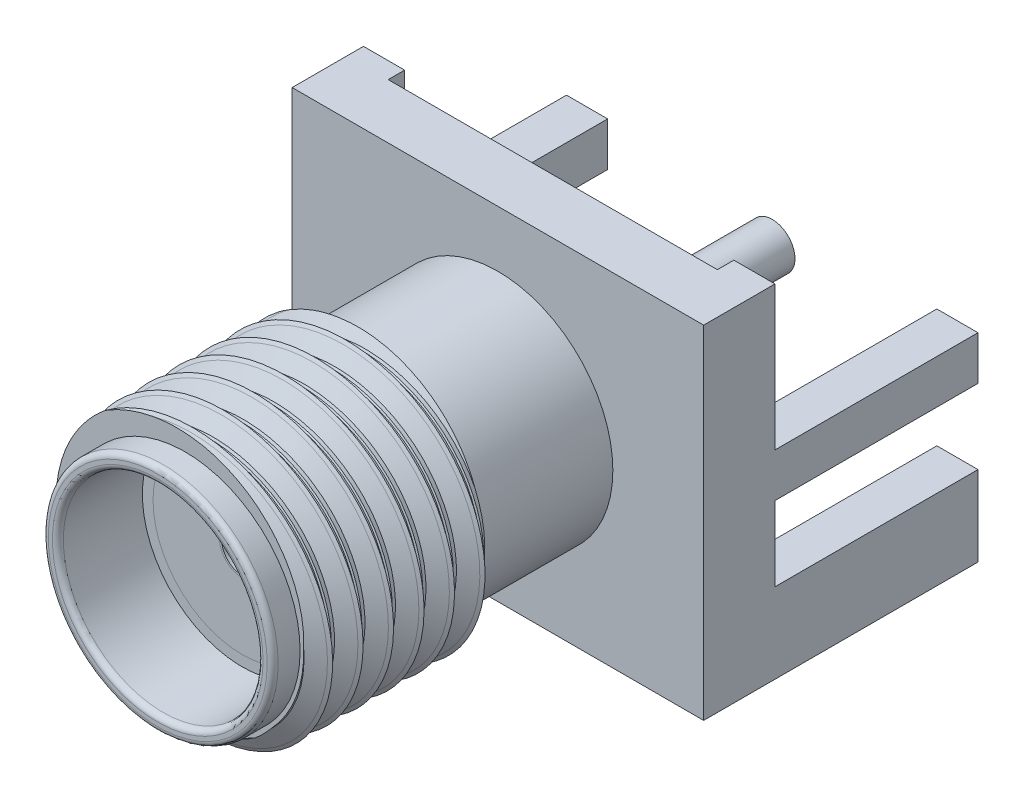
SolidWorks part; units mm, degrees
material "Brass"
ref_plane "Front Plane" through (0, 0, 0) normal (0, 0, 1) x (1, 0, 0)
ref_plane "Top Plane" through (0, 0, 0) normal (0, 1, 0) x (1, 0, 0)
ref_plane "Right Plane" through (0, 0, 0) normal (1, 0, 0) x (0, 0, -1)
sketch "Sketch1" plane through (0, 0, 0) normal (0, 0, 1) x (1, 0, 0)
  circle A0 centre (0, 0) radius 2.6607
  dimension "D1" = 5.3213
extrude "Boss-Extrude1" add sketch "Sketch1" along normal blind 7.874
sketch "Sketch2" plane through (0, 0, 7.874) normal (0, 0, 1) x (1, 0, 0)
  circle A0 centre (0, 0) radius 2.3114
  dimension "D1" = 4.6228
extrude "Cut-Extrude1" cut sketch "Sketch2" against normal blind 1.9558
sketch "Sketch5" plane through (0, 0, 0) normal (0, 0, -1) x (-1, 0, 0)
  line L0 (0, 2.6607) -> (0, 3.9624) construction
  line L1 (-4.7625, 3.9624) -> (4.7625, 3.9624)
  line L2 (-4.7625, 3.9624) -> (-4.7625, -3.9624)
  line L3 (-4.7625, -3.9624) -> (4.7625, -3.9624)
  line L4 (4.7625, 3.9624) -> (4.7625, -3.9624)
  line L5 (2.6607, 0) -> (4.7625, 0) construction
  circle A0 centre (0, 0) radius 2.6607 construction
  circle A1 centre (0, 0) radius 2.6607 construction
  circle A2 centre (0, 0) radius 2.032
  dimension "D3" = 4.064
  dimension "D1" = 9.525
  dimension "D2" = 7.9248
extrude "Boss-Extrude2" add sketch "Sketch5" along normal blind 1.651 separate body
sketch "Sketch6" plane through (0, 3.9624, 0) normal (0, 1, 0) x (1, 0, 0)
  line L0 (-4.7625, 1.651) -> (4.7625, 1.651) construction
  line L1 (-3.81, 1.651) -> (3.81, 1.651)
  line L2 (-3.81, 1.651) -> (-3.81, 1.27)
  line L3 (-3.81, 1.27) -> (3.81, 1.27)
  line L4 (3.81, 1.651) -> (3.81, 1.27)
  line L5 (-4.7625, 0) -> (4.7625, 0) construction
  line L6 (0, 1.27) -> (0, 0) construction
  dimension "D1" = 1.27
  dimension "D2" = 7.62
extrude "Cut-Extrude2" cut sketch "Sketch6" against normal through all
sketch "Sketch7" plane through (0, 0, 5.9182) normal (0, 0, 1) x (1, 0, 0)
  circle A0 centre (0, 0) radius 0.4763
  dimension "D1" = 0.9525
extrude "Cut-Extrude3" cut sketch "Sketch7" against normal through all
sketch "Sketch8" plane through (0, 0, 5.9182) normal (0, 0, 1) x (1, 0, 0)
  circle A0 centre (0, 0) radius 2.0638
  circle A4 centre (0, 0) radius 0.5259
  circle A5 centre (0, 0) radius 0.5259
  dimension "D1" = 4.1275
  dimension "D2" = 0.0496
split line "Split Line1"
sketch "Sketch9" plane through (0, 0, 0) normal (0, 0, 1) x (1, 0, 0)
  circle A0 centre (0, 0) radius 0.5259 construction
  circle A1 centre (0, 0) radius 0.5259
extrude "Boss-Extrude4" add sketch "Sketch9" against normal offset from surface (6.35 mm away) 5.08 separate body up to face at (2.032, 0, -1.27) offset beyond the face yes
sketch "Sketch10" plane through (0, 0, -1.651) normal (0, 0, -1) x (-1, 0, 0)
  line L0 (3.81, -3.9624) -> (3.81, 3.9624) construction
  line L1 (3.81, 0.635) -> (4.7625, 0.635)
  line L2 (3.81, 0.635) -> (3.81, -0.381)
  line L3 (3.81, -0.381) -> (4.7625, -0.381)
  line L4 (4.7625, 0.635) -> (4.7625, -0.381)
  line L5 (4.7625, -3.9624) -> (4.7625, 3.9624) construction
  line L7 (3.81, -2.1082) -> (4.7625, -2.1082)
  line L8 (3.81, -2.1082) -> (3.81, -3.9624)
  line L9 (3.81, -3.9624) -> (4.7625, -3.9624)
  line L10 (4.7625, -2.1082) -> (4.7625, -3.9624)
  line L11 (3.81, -3.9624) -> (4.7625, -3.9624) construction
  line L12 (0, -1000) -> (0, 49000) construction
  line L13 (-4.7625, -2.1082) -> (-4.7625, -3.9624)
  line L14 (-3.81, -3.9624) -> (-4.7625, -3.9624)
  line L15 (-3.81, -2.1082) -> (-3.81, -3.9624)
  line L16 (-3.81, -2.1082) -> (-4.7625, -2.1082)
  line L17 (-4.7625, 0.635) -> (-4.7625, -0.381)
  line L18 (-3.81, -0.381) -> (-4.7625, -0.381)
  line L19 (-3.81, 0.635) -> (-3.81, -0.381)
  line L20 (-3.81, 0.635) -> (-4.7625, 0.635)
  dimension "D1" = 1.016
  dimension "D2" = 1.7272
  dimension "D3" = 1.8542
extrude "Boss-Extrude5" add sketch "Sketch10" along normal up to surface (4.699 mm away) up to face at (0.5259, 0, -6.35)
sketch "Sketch12" plane through (0, 0, 7.874) normal (0, 0, 1) x (1, 0, 0)
  circle A1 centre (0, 0) radius 3.1636
  dimension "MajorDiameter" = 6.3271
sketch "Sketch13" plane through (0, 0, 7.874) normal (0, 0, 1) x (1, 0, 0)
  circle A0 centre (0, 0) radius 3.1636
  circle A1 centre (0, 0) radius 2.6607
  circle A2 centre (0, 0) radius 2.6607 construction
  dimension "MajorDiameter" = 6.3271
extrude "Boss-Extrude6" add sketch "Sketch13" against normal blind 4.191 from offset 0.635 offset against normal yes
curve "Helix/Spiral1" pitch 0.7056 height 7.0556 radius 3.1636 centre (0, 0, 7.874) axis (0, 0, -1) start towards (0, 1, 0) parameters "Pitch"=0.7056
sketch "Sketch15" plane through (0, 0, 0) normal (1, 0, 0) x (0, 0, -1)
  line L0 (-7.874, 3.1636) -> (-7.874, -3.1636) construction
  line L1 (-6.4629, 3.1636) -> (-7.1684, 3.1636) construction
  line L2 (-7.1684, 3.1636) -> (-7.874, 3.1636) construction
  line L3 (-10.4133, 2.7445) -> (0, 2.7445) construction
  line L4 (-10.4133, 2.7445) -> (-10.4133, -2.7445) construction
  line L5 (-7.874, 0) -> (-10.4133, 0) construction
  line L6 (0, 3.9624) -> (0, -3.9624) construction
  line L7 (-6.4629, 3.1636) -> (-5.7573, 3.1636) construction
  line L8 (-8.4915, 3.0883) -> (-8.4033, 3.0883) construction
  line L9 (-8.4033, 3.0883) -> (-8.2048, 2.7445)
  line L10 (-8.2048, 2.7445) -> (-8.1166, 2.7445)
  line L11 (-7.874, 2.6607) -> (-7.874, -2.6607) construction
  line L12 (-3.048, 3.1636) -> (-7.239, 3.1636) construction
  line L13 (-8.1166, 2.7445) -> (-7.9181, 3.0883)
  line L14 (-7.9181, 3.0883) -> (-7.8299, 3.0883) construction
  line L15 (-7.8299, 3.0883) -> (-7.6314, 2.7445)
  line L16 (-7.6314, 2.7445) -> (-7.5432, 2.7445)
  line L17 (-7.5432, 2.7445) -> (-7.3447, 3.0883)
  line L18 (-7.3447, 3.0883) -> (-7.2565, 3.0883) construction
  line L19 (-8.1607, 2.7445) -> (-8.1607, 3.9348) construction
  line L20 (-7.9181, 3.0883) -> (-8.4033, 3.0883) construction
  line L21 (-7.5873, 2.7445) -> (-7.5873, 3.9348) construction
  line L22 (-7.3447, 3.0883) -> (-7.8299, 3.0883) construction
  line L23 (-7.874, 3.1636) -> (-7.874, 3.9348) construction
  line L24 (-7.9181, 3.0883) -> (-7.874, 3.1636)
  line L25 (-7.874, 3.1636) -> (-7.8299, 3.0883)
  line L26 (-7.3447, 3.0883) -> (-7.3447, 4.147)
  line L27 (-7.3447, 4.147) -> (-8.4033, 4.147)
  line L28 (-8.4033, 4.147) -> (-8.4033, 3.0883)
  spline S0 degree 3 poles (30.3197, -1996.2874) (-9.6986, -238.0579) (-8.6725, 16.4609) (-7.7858, 2.2952) (-7.7417, 1.2422) (-7.6976, 0) (-7.6535, -1.2422) (-7.6094, -2.2952) (-7.5653, -2.9988) (-7.5212, -3.2459) (-7.4771, -2.9988) (-7.433, -2.2952) (-7.3889, -1.2422) (-7.3448, 0) (-7.3007, 1.2422) (-7.2566, 2.2952) (-7.2125, 2.9988) (-7.1684, 3.2459) (-7.1243, 2.9988) (-7.0803, 2.2952) (-7.0362, 1.2422) (-6.9921, 0) (-6.948, -1.2422) (-6.9039, -2.2952) (-6.8598, -2.9988) (-6.8157, -3.2459) (-6.7716, -2.9988) (-6.7275, -2.2952) (-6.6834, -1.2422) (-6.6393, 0) (-6.5952, 1.2422) (-6.5511, 2.2952) (-6.507, 2.9988) (-6.4629, 3.2459) (-6.4188, 2.9988) (-6.3747, 2.2952) (-6.3306, 1.2422) (-6.2865, 0) (-6.2424, -1.2422) (-6.1983, -2.2952) (-6.1542, -2.9988) (-6.1101, -3.2459) (-6.066, -2.9988) (-6.0219, -2.2952) (-5.9778, -1.2422) (-5.9337, 0) (-5.8896, 1.2422) (-5.8455, 2.2952) (-5.8014, 2.9988) (-5.7573, 3.2459) (-5.7132, 2.9988) (-5.6691, 2.2952) (-5.625, 1.2422) (-5.5809, 0) (-5.5368, -1.2422) (-5.4927, -2.2952) (-5.4487, -2.9988) (-5.4046, -3.2459) (-5.3605, -2.9988) (-5.3164, -2.2952) (-5.2723, -1.2422) (-5.2282, 0) (-5.1841, 1.2422) (-5.14, 2.2952) (-5.0959, 2.9988) (-5.0518, 3.2459) (-5.0077, 2.9988) (-4.9636, 2.2952) (-4.9195, 1.2422) (-4.8754, 0) (-4.8313, -1.2422) (-4.7872, -2.2952) (-4.7431, -2.9988) (-4.699, -3.2459) (-4.6549, -2.9988) (-4.6108, -2.2952) (-4.5667, -1.2422) (-4.5226, 0) (-4.4785, 1.2422) (-4.4344, 2.2952) (-4.3903, 2.9988) (-4.3462, 3.2459) (-4.3021, 2.9988) (-4.258, 2.2952) (-4.2139, 1.2422) (-4.1698, 0) (-4.1257, -1.2422) (-4.0816, -2.2952) (-4.0375, -2.9988) (-3.9934, -3.2459) (-3.9493, -2.9988) (-3.9052, -2.2952) (-3.8612, -1.2422) (-3.8171, 0) (-3.773, 1.2422) (-3.7289, 2.2952) (-3.6848, 2.9988) (-3.6407, 3.2459) (-3.5966, 2.9988) (-3.5525, 2.2952) (-3.5084, 1.2422) (-3.4643, 0) (-3.4202, -1.2422) (-3.3761, -2.2952) (-3.332, -2.9988) (-3.2879, -3.2459) (-3.2438, -2.9988) (-3.1997, -2.2952) (-3.1556, -1.2422) (-3.1115, 0) (-3.0674, 1.2422) (-3.0233, 2.2952) (-2.9792, 2.9988) (-2.9351, 3.2459) (-2.891, 2.9988) (-2.8469, 2.2952) (-2.8028, 1.2422) (-2.7587, 0) (-2.7146, -1.2422) (-2.6705, -2.2952) (-2.6264, -2.9988) (-2.5823, -3.2459) (-2.5382, -2.9988) (-2.4941, -2.2952) (-2.45, -1.2422) (-2.4059, 0) (-2.3618, 1.2422) (-2.3177, 2.2952) (-2.2737, 2.9988) (-2.2296, 3.2459) (-2.1855, 2.9988) (-2.1414, 2.2952) (-2.0973, 1.2422) (-2.0532, 0) (-2.0091, -1.2422) (-1.965, -2.2952) (-1.9209, -2.9988) (-1.8768, -3.2459) (-1.8327, -2.9988) (-1.7886, -2.2952) (-1.7445, -1.2422) (-1.7004, 0) (-1.6563, 1.2422) (-1.6122, 2.2952) (-1.5681, 2.9988) (-1.524, 3.2459) (-1.4799, 2.9988) (-1.4358, 2.2952) (-1.3917, 1.2422) (-1.3476, 0) (-1.3035, -1.2422) (-1.2594, -2.2952) (-1.2153, -2.9988) (-1.1712, -3.2459) (-1.1271, -2.9988) (-1.083, -2.2952) (-1.0389, -1.2422) (-0.9948, 0) (-0.9507, 1.2422) (-0.9066, 2.2952) (-0.02, 16.461) (1.0062, -238.0612) (-39.0129, -1996.3232) knots -0.358731 -0.358731 -0.358731 -0.358731 0.00625 0.0125 0.01875 0.025 0.03125 0.0375 0.04375 0.05 0.05625 0.0625 0.06875 0.075 0.08125 0.0875 0.09375 0.1 0.10625 0.1125 0.11875 0.125 0.13125 0.1375 0.14375 0.15 0.15625 0.1625 0.16875 0.175 0.18125 0.1875 0.19375 0.2 0.20625 0.2125 0.21875 0.225 0.23125 0.2375 0.24375 0.25 0.25625 0.2625 0.26875 0.275 0.28125 0.2875 0.29375 0.3 0.30625 0.3125 0.31875 0.325 0.33125 0.3375 0.34375 0.35 0.35625 0.3625 0.36875 0.375 0.38125 0.3875 0.39375 0.4 0.40625 0.4125 0.41875 0.425 0.43125 0.4375 0.44375 0.45 0.45625 0.4625 0.46875 0.475 0.48125 0.4875 0.49375 0.5 0.50625 0.5125 0.51875 0.525 0.53125 0.5375 0.54375 0.55 0.55625 0.5625 0.56875 0.575 0.58125 0.5875 0.59375 0.6 0.60625 0.6125 0.61875 0.625 0.63125 0.6375 0.64375 0.65 0.65625 0.6625 0.66875 0.675 0.68125 0.6875 0.69375 0.7 0.70625 0.7125 0.71875 0.725 0.73125 0.7375 0.74375 0.75 0.75625 0.7625 0.76875 0.775 0.78125 0.7875 0.79375 0.8 0.80625 0.8125 0.81875 0.825 0.83125 0.8375 0.84375 0.85 0.85625 0.8625 0.86875 0.875 0.88125 0.8875 0.89375 0.9 0.90625 0.9125 0.91875 0.925 0.93125 0.9375 0.94375 0.95 0.95625 0.9625 0.96875 0.975 0.98125 0.9875 0.99375 1.358734 1.358734 1.358734 1.358734 only from (-7.874, 3.1636) to (-0.8184, 3.1636) construction
  spline S1 degree 3 poles (-7.874, 3.1636) (-7.8594, 3.1636) (-7.8299, 2.9988) (-7.7858, 2.2952) (-7.7417, 1.2422) (-7.6976, 0) (-7.6535, -1.2422) (-7.6094, -2.2952) (-7.5653, -2.9988) (-7.5212, -3.2459) (-7.4771, -2.9988) (-7.433, -2.2952) (-7.3889, -1.2422) (-7.3448, 0) (-7.3007, 1.2422) (-7.2566, 2.2952) (-7.2125, 2.9988) (-7.1684, 3.2459) (-7.1243, 2.9988) (-7.0803, 2.2952) (-7.0362, 1.2422) (-6.9921, 0) (-6.948, -1.2422) (-6.9039, -2.2952) (-6.8598, -2.9988) (-6.8157, -3.2459) (-6.7716, -2.9988) (-6.7275, -2.2952) (-6.6834, -1.2422) (-6.6393, 0) (-6.5952, 1.2422) (-6.5511, 2.2952) (-6.507, 2.9988) (-6.4629, 3.2459) (-6.4188, 2.9988) (-6.3747, 2.2952) (-6.3306, 1.2422) (-6.2865, 0) (-6.2424, -1.2422) (-6.1983, -2.2952) (-6.1542, -2.9988) (-6.1101, -3.2459) (-6.066, -2.9988) (-6.0219, -2.2952) (-5.9778, -1.2422) (-5.9337, 0) (-5.8896, 1.2422) (-5.8455, 2.2952) (-5.8014, 2.9988) (-5.7573, 3.2459) (-5.7132, 2.9988) (-5.6691, 2.2952) (-5.625, 1.2422) (-5.5809, 0) (-5.5368, -1.2422) (-5.4927, -2.2952) (-5.4487, -2.9988) (-5.4046, -3.2459) (-5.3605, -2.9988) (-5.3164, -2.2952) (-5.2723, -1.2422) (-5.2282, 0) (-5.1841, 1.2422) (-5.14, 2.2952) (-5.0959, 2.9988) (-5.0518, 3.2459) (-5.0077, 2.9988) (-4.9636, 2.2952) (-4.9195, 1.2422) (-4.8754, 0) (-4.8313, -1.2422) (-4.7872, -2.2952) (-4.7431, -2.9988) (-4.699, -3.2459) (-4.6549, -2.9988) (-4.6108, -2.2952) (-4.5667, -1.2422) (-4.5226, 0) (-4.4785, 1.2422) (-4.4344, 2.2952) (-4.3903, 2.9988) (-4.3462, 3.2459) (-4.3021, 2.9988) (-4.258, 2.2952) (-4.2139, 1.2422) (-4.1698, 0) (-4.1257, -1.2422) (-4.0816, -2.2952) (-4.0375, -2.9988) (-3.9934, -3.2459) (-3.9493, -2.9988) (-3.9052, -2.2952) (-3.8612, -1.2422) (-3.8171, 0) (-3.773, 1.2422) (-3.7289, 2.2952) (-3.6848, 2.9988) (-3.6407, 3.2459) (-3.5966, 2.9988) (-3.5525, 2.2952) (-3.5084, 1.2422) (-3.4643, 0) (-3.4202, -1.2422) (-3.3761, -2.2952) (-3.332, -2.9988) (-3.2879, -3.2459) (-3.2438, -2.9988) (-3.1997, -2.2952) (-3.1556, -1.2422) (-3.1115, 0) (-3.0674, 1.2422) (-3.0233, 2.2952) (-2.9792, 2.9988) (-2.9351, 3.2459) (-2.891, 2.9988) (-2.8469, 2.2952) (-2.8028, 1.2422) (-2.7587, 0) (-2.7146, -1.2422) (-2.6705, -2.2952) (-2.6264, -2.9988) (-2.5823, -3.2459) (-2.5382, -2.9988) (-2.4941, -2.2952) (-2.45, -1.2422) (-2.4059, 0) (-2.3618, 1.2422) (-2.3177, 2.2952) (-2.2737, 2.9988) (-2.2296, 3.2459) (-2.1855, 2.9988) (-2.1414, 2.2952) (-2.0973, 1.2422) (-2.0532, 0) (-2.0091, -1.2422) (-1.965, -2.2952) (-1.9209, -2.9988) (-1.8768, -3.2459) (-1.8327, -2.9988) (-1.7886, -2.2952) (-1.7445, -1.2422) (-1.7004, 0) (-1.6563, 1.2422) (-1.6122, 2.2952) (-1.5681, 2.9988) (-1.524, 3.2459) (-1.4799, 2.9988) (-1.4358, 2.2952) (-1.3917, 1.2422) (-1.3476, 0) (-1.3035, -1.2422) (-1.2594, -2.2952) (-1.2153, -2.9988) (-1.1712, -3.2459) (-1.1271, -2.9988) (-1.083, -2.2952) (-1.0389, -1.2422) (-0.9948, 0) (-0.9507, 1.2422) (-0.9066, 2.2952) (-0.8626, 2.9988) (-0.833, 3.1636) (-0.8184, 3.1636) knots 0 0 0 0 0.00625 0.0125 0.01875 0.025 0.03125 0.0375 0.04375 0.05 0.05625 0.0625 0.06875 0.075 0.08125 0.0875 0.09375 0.1 0.10625 0.1125 0.11875 0.125 0.13125 0.1375 0.14375 0.15 0.15625 0.1625 0.16875 0.175 0.18125 0.1875 0.19375 0.2 0.20625 0.2125 0.21875 0.225 0.23125 0.2375 0.24375 0.25 0.25625 0.2625 0.26875 0.275 0.28125 0.2875 0.29375 0.3 0.30625 0.3125 0.31875 0.325 0.33125 0.3375 0.34375 0.35 0.35625 0.3625 0.36875 0.375 0.38125 0.3875 0.39375 0.4 0.40625 0.4125 0.41875 0.425 0.43125 0.4375 0.44375 0.45 0.45625 0.4625 0.46875 0.475 0.48125 0.4875 0.49375 0.5 0.50625 0.5125 0.51875 0.525 0.53125 0.5375 0.54375 0.55 0.55625 0.5625 0.56875 0.575 0.58125 0.5875 0.59375 0.6 0.60625 0.6125 0.61875 0.625 0.63125 0.6375 0.64375 0.65 0.65625 0.6625 0.66875 0.675 0.68125 0.6875 0.69375 0.7 0.70625 0.7125 0.71875 0.725 0.73125 0.7375 0.74375 0.75 0.75625 0.7625 0.76875 0.775 0.78125 0.7875 0.79375 0.8 0.80625 0.8125 0.81875 0.825 0.83125 0.8375 0.84375 0.85 0.85625 0.8625 0.86875 0.875 0.88125 0.8875 0.89375 0.9 0.90625 0.9125 0.91875 0.925 0.93125 0.9375 0.94375 0.95 0.95625 0.9625 0.96875 0.975 0.98125 0.9875 0.99375 1 1 1 1 construction
  point P29 (-8.1607, 3.0883)
  point P32 (-7.5873, 3.0883)
  point P33 (-7.874, 3.0883)
  dimension "D1" = 60
  dimension "D2" = 0.5734
  dimension "MajorDiameter" = 6.3271
  dimension "MinorDiameter" = 5.4889
  dimension "8thPitch" = 0.0882
sweep "Cut-Sweep5" cut profiles "Sketch15" path "Helix/Spiral1" align with end faces yes
fillet "Fillet1" radius 0.127 2 edges at (2.3114, 0, 7.874) (2.6607, 0, 7.874)
equation "\"MajorDiameter\"= 0.2491"
equation "\"MinorDiameter\"= 0.2161"
equation "\"Theta\"= 60"
equation "\"Pitch\"= 1/36 "
equation "\"8thPitch\"= \"Pitch\"/8"
